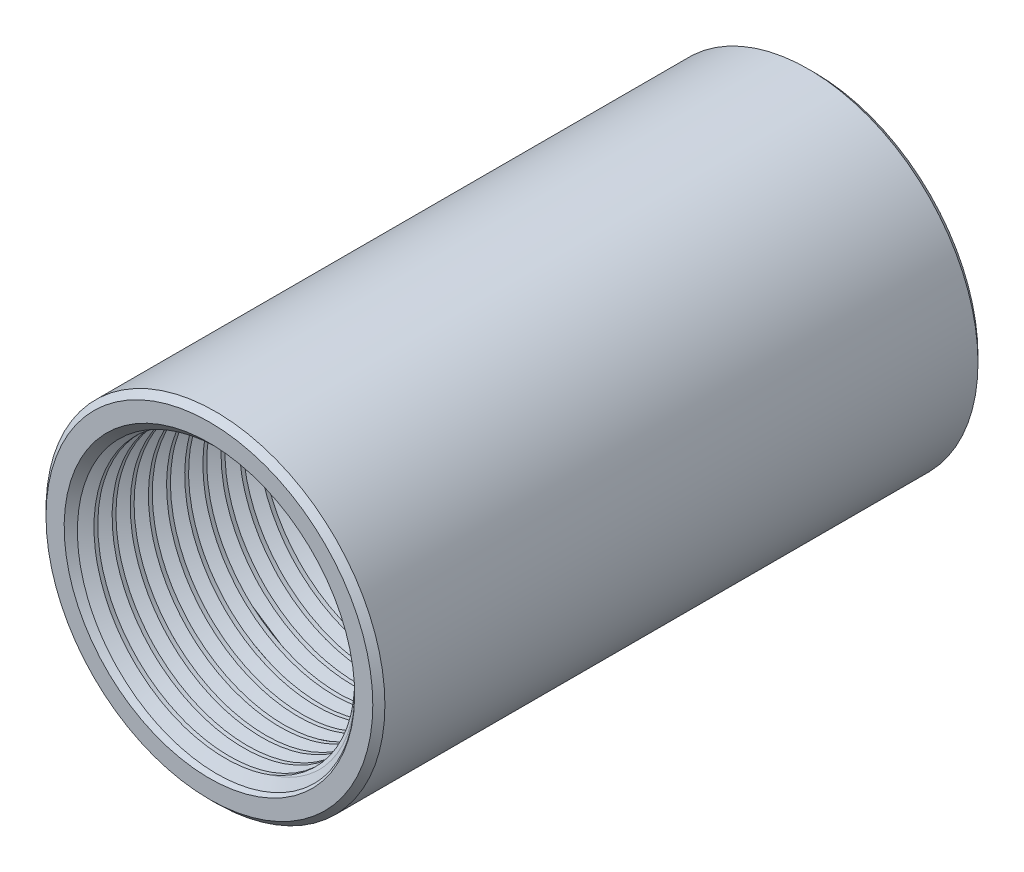
SolidWorks part; units mm, degrees
ref_plane "前视基准面" through (0, 0, 0) normal (0, 0, 1) x (1, 0, 0)
ref_plane "上视基准面" through (0, 0, 0) normal (0, 1, 0) x (1, 0, 0)
ref_plane "右视基准面" through (0, 0, 0) normal (1, 0, 0) x (0, 0, -1)
ref_plane "基准面1" through (0, 0, 25) normal (0, 0, 1) x (1, 0, 0)
sketch "草图1" plane through (0, 0, 0) normal (0, 0, 1) x (1, 0, 0)
  circle A0 centre (0, 0) radius 14
  dimension "D1" = 28
extrude "拉伸1" add sketch "草图1" along normal blind 50
shell "抽壳1" thickness 3
chamfer "倒角1" distance 0.5 angle 45 2 edges at (14, 0, 50) (14, 0, 0)
sketch "草图5" plane through (0, 0, 0) normal (0, 0, -1) x (-1, 0, 0)
  circle A0 centre (0, 0) radius 11
curve "螺旋线/涡状线1" pitch 1.5 height 55.5 turns 37
chamfer "倒角2" distance 1 angle 45 2 edges at (11, 0, 50) (11, 0, 0)
sketch "草图6" plane through (0, 0, 0) normal (1, 0, 0) x (0, 0, -1)
  line L0 (0, -8.0324) -> (0, -15.7237) construction
  line L1 (0, -13.5) -> (0, 13.5) construction
  line L2 (-1.8171, -11) -> (2.1386, -11) construction
  line L3 (-49, -11) -> (-1, -11) construction
  line L4 (-0.65, -10.9) -> (0.65, -10.9)
  line L5 (0.65, -10.9) -> (0, -12)
  line L6 (0, -12) -> (-0.65, -10.9)
  dimension "D1" = 1.3
  dimension "D2" = 1.1
  dimension "D3" = 0.1
sweep "切除-扫描1" cut profiles "草图6" path "螺旋线/涡状线1"
